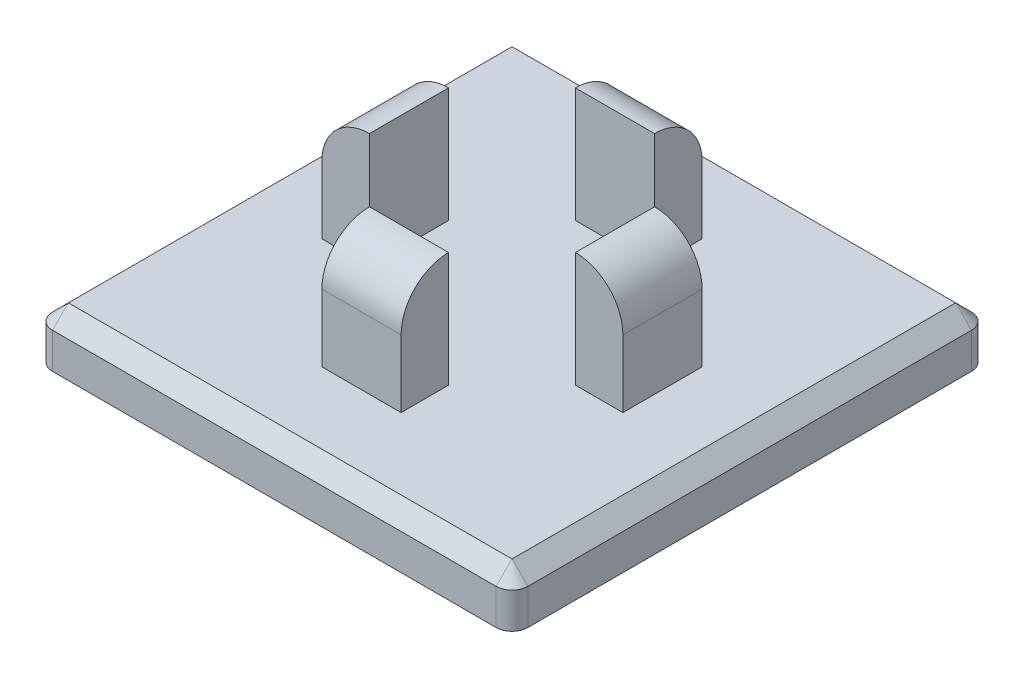
SolidWorks part; units mm, degrees
ref_plane "Front Plane" through (0, 0, 0) normal (0, 0, 1) x (1, 0, 0)
ref_plane "Top Plane" through (0, 0, 0) normal (0, 1, 0) x (1, 0, 0)
ref_plane "Right Plane" through (0, 0, 0) normal (1, 0, 0) x (0, 0, -1)
sketch "Sketch1" plane through (0, 0, 0) normal (0, 1, 0) x (1, 0, 0)
  line L0 (-7.62, 7.112) -> (-7.62, -7.112)
  line L1 (-7.112, -7.62) -> (7.112, -7.62)
  line L2 (7.62, -7.112) -> (7.62, 7.112)
  line L3 (7.112, 7.62) -> (-7.112, 7.62)
  line L4 (-1.27, 4.826) -> (1.27, 4.826)
  line L5 (1.27, 4.826) -> (1.27, 3.302)
  line L6 (1.27, 3.302) -> (-1.27, 3.302)
  line L7 (-1.27, 3.302) -> (-1.27, 4.826)
  line L8 (3.302, 1.27) -> (4.826, 1.27)
  line L9 (4.826, 1.27) -> (4.826, -1.27)
  line L10 (4.826, -1.27) -> (3.302, -1.27)
  line L11 (3.302, -1.27) -> (3.302, 1.27)
  line L12 (1.27, -3.302) -> (1.27, -4.826)
  line L13 (1.27, -4.826) -> (-1.27, -4.826)
  line L14 (-1.27, -4.826) -> (-1.27, -3.302)
  line L15 (-1.27, -3.302) -> (1.27, -3.302)
  line L16 (-3.302, -1.27) -> (-4.826, -1.27)
  line L17 (-4.826, -1.27) -> (-4.826, 1.27)
  line L18 (-4.826, 1.27) -> (-3.302, 1.27)
  line L19 (-3.302, 1.27) -> (-3.302, -1.27)
  arc A0 (-7.62, -7.112) -> (-7.112, -7.62) centre (-7.112, -7.112) ccw
  arc A1 (7.112, -7.62) -> (7.62, -7.112) centre (7.112, -7.112) ccw
  arc A2 (7.62, 7.112) -> (7.112, 7.62) centre (7.112, 7.112) ccw
  arc A3 (-7.112, 7.62) -> (-7.62, 7.112) centre (-7.112, 7.112) ccw
  circle A4 centre (0, 0) radius 4.064
  point P37 (0, 0)
  dimension "D1" = 0.508
  dimension "D3" = 8.128
  dimension "D2" = 4
  dimension "D4" = 4.826
  dimension "D5" = 1.524
  dimension "D6" = 2.54
extrude "Boss-Extrude1" add sketch "Sketch1" along normal blind 1.651 contours L3 A3 L0 A0 L1 A1 L2 A2 A4 L12 L13 L14 L16 L17 L18 L7 L4 L5 L8 L9 L10 | L12 A4 L10 L11 L8 L5 L6 L7 L18 L19 L16 L14 L15 region at (-7.3188, 0, -7.3188) region at (0, 0, 0)
extrude "Boss-Extrude2" add sketch "Sketch1<3>" along normal blind 5.334 contours A4 L18 L17 L16 | L18 A4 L16 L19 | L14 A4 L12 L15 | A4 L14 L13 L12 | L5 A4 L7 L6 | A4 L5 L4 L7 | A4 L10 L9 L8 | L10 A4 L8 L11 region at (0, 0, -4.4092) region at (0, 0, -3.6521) region at (-4.4092, 0, 0) region at (-3.6521, 0, 0) region at (3.6521, 0, 0) region at (4.4092, 0, 0) region at (0, 0, 4.4092) region at (0, 0, 3.6521)
sketch "Sketch1<3>" plane through (0, 0, 0) normal (0, 1, 0) x (1, 0, 0) same geometry as "Sketch1"
fillet "Fillet1" radius 1.524 4 edges at (-4.826, 5.334, 0) (0, 5.334, -4.826) (4.826, 5.334, 0) (0, 5.334, 4.826)
chamfer "Chamfer1" distance 0.508 angle 45 8 edges at (7.62, 1.651, 0) (0, 1.651, -7.62) (-7.62, 1.651, 0) (-7.4712, 1.651, -7.4712) (7.4712, 1.651, -7.4712) (-7.4712, 1.651, 7.4712) (7.4712, 1.651, 7.4712) (0, 1.651, 7.62)
